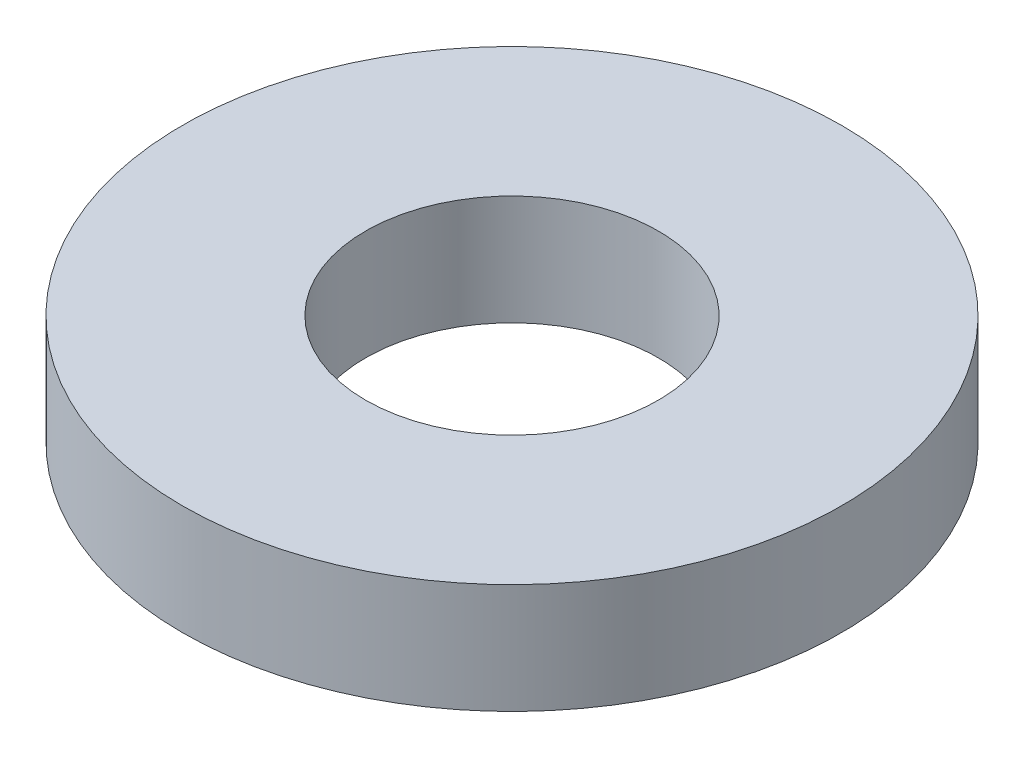
SolidWorks part; units mm, degrees
ref_plane "Front Plane" through (0, 0, 0) normal (0, 0, 1) x (1, 0, 0)
ref_plane "Top Plane" through (0, 0, 0) normal (0, 1, 0) x (1, 0, 0)
ref_plane "Right Plane" through (0, 0, 0) normal (1, 0, 0) x (0, 0, -1)
sketch "Sketch1" plane through (0, 0, 0) normal (0, 1, 0) x (1, 0, 0)
  circle A0 centre (0, 0) radius 90
  dimension "FLANGE_OD" = 180
extrude "Boss-Extrude1" add sketch "Sketch1" along normal blind 30
sketch "Sketch2" plane through (0, 0, 0) normal (0, 1, 0) x (1, 0, 0)
  circle A0 centre (0, 0) radius 40
  dimension "BORE_D" = 80
extrude "Cut-Extrude1" cut sketch "Sketch2" along normal through all
sketch "Sketch3" plane through (0, 30, 0) normal (0, 1, 0) x (1, 0, 0)
  circle A0 centre (0, 0) radius 31.6498 construction
  circle A1 centre (-31.6498, 0) radius 4.1219
  dimension "BOLT_D" = 8.2437
  dimension "BOLT_PCD" = 63.2997
extrude "Cut-Extrude2" cut sketch "Sketch3" against normal blind 18.5975 rebuild error yes
pattern_circular "CirPattern1" count 6 over 360 rebuild error yes
